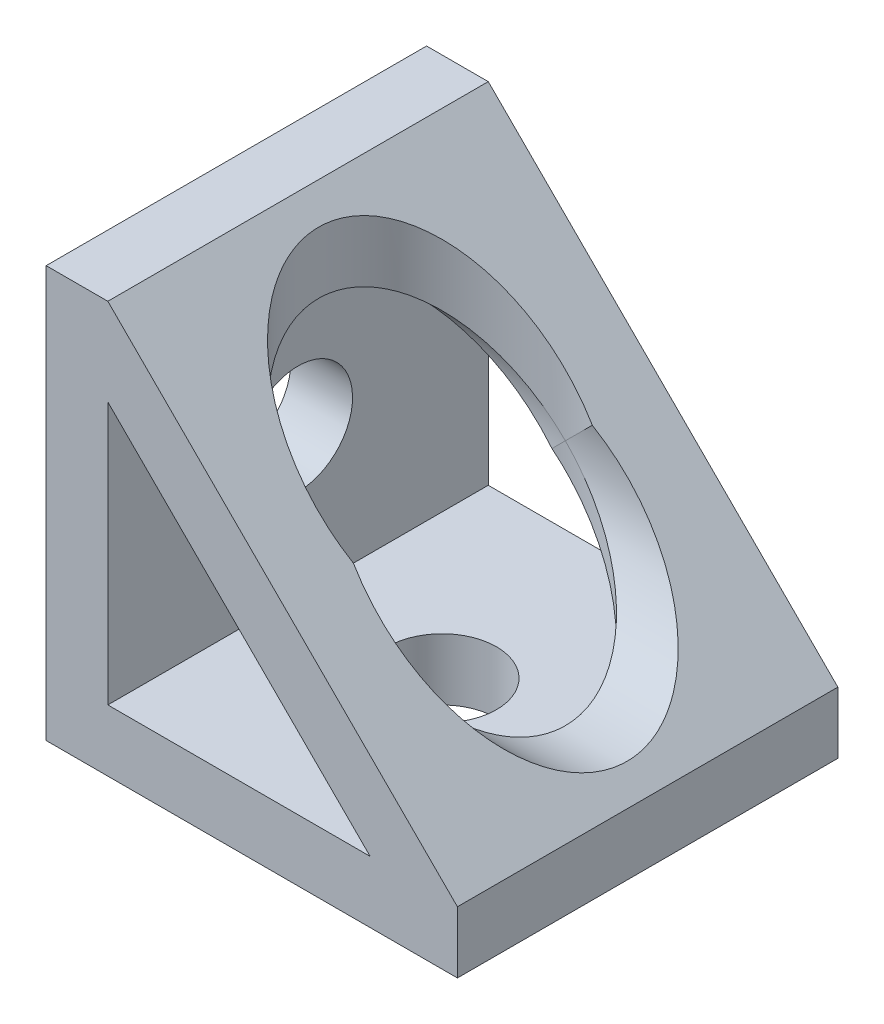
SolidWorks part; units mm, degrees
ref_plane "Front Plane" through (0, 0, 0) normal (0, 0, 1) x (1, 0, 0)
ref_plane "Top Plane" through (0, 0, 0) normal (0, 1, 0) x (1, 0, 0)
ref_plane "Right Plane" through (0, 0, 0) normal (1, 0, 0) x (0, 0, -1)
sketch "Sketch1" plane through (0, 0, 0) normal (0, 0, 1) x (1, 0, 0)
  line L0 (0, 10) -> (0, -10) construction
  line L1 (10, 0) -> (-10, 0) construction
  line L2 (-2.65, -10) -> (2.65, -10) construction
  line L3 (-10, -10) -> (-10, -7) construction
  line L4 (-6, -7) -> (6, -7) construction
  point P4 (0, 0)
  point P8 (0, 0)
  point P11 (0, -10)
  point P16 (0, -7)
  dimension "Length" = 20
  dimension "Clearance Hole" = 5.3
  dimension "Wall" = 3
  dimension "Access Hole" = 12
  dimension "For Rail Height" = 20
sketch "Sketch3" plane through (0, 0, 0) normal (1, 0, 0) x (0, 0, -1)
  line L0 (9.25, 0) -> (-9.25, 0) construction
  point P3 (0, 0)
  dimension "Thickness" = 18.5
sketch "Sketch2" plane through (0, 0, 0) normal (0, 0, 1) x (1, 0, 0)
  line L0 (-10, 10) -> (-10, -10)
  line L1 (-10, -10) -> (10, -10)
  line L3 (-2.65, -10) -> (2.65, -10) construction
  line L4 (-10, -10) -> (-10, -7) construction
  line L5 (10, -10) -> (10, -7)
  line L6 (10, -7) -> (-7, 10)
  line L7 (-7, 10) -> (-10, 10)
  line L8 (-7, 5.7574) -> (-7, -7)
  line L9 (-7, -7) -> (5.7574, -7)
  line L10 (5.7574, -7) -> (5.7574, -7)
  line L11 (5.7574, -7) -> (-7, 5.7574)
  line L12 (-7, 5.7574) -> (-7, 5.7574)
extrude "Boss-Extrude1" add sketch "Sketch2" against normal up to vertex (9.25 mm away) and the other way up to vertex (9.25 mm away) up to point (0, 0, -9.25) other way up to point (0, 0, 9.25)
sketch "Sketch4" plane through (0, -10, 0) normal (0, -1, 0) x (1, 0, 0)
  line L0 (-2.65, 0) -> (2.65, 0) construction
  line L1 (-2.65, 0) -> (2.65, 0) construction
  circle A0 centre (0, 0) radius 2.65
extrude "Cut-Extrude1" cut sketch "Sketch4" against normal up to next
sketch "Sketch6" plane through (0, -7, 0) normal (0, 1, 0) x (1, 0, 0)
  circle A0 centre (0, 0) radius 6
extrude "Cut-Extrude2" cut sketch "Sketch6" along normal through all
ref_plane "Plane1" through (0, 0, 0) normal (0.7071, -0.7071, 0) x (-0.7071, -0.7071, 0)
mirror "Mirror1" about plane through (0, 0, 0) normal (0.7071, -0.7071, 0) of "Cut-Extrude2", "Cut-Extrude1"
sketch "Sketch7" plane through (0, -7, 0) normal (0, 1, 0) x (1, 0, 0)
  line L0 (0, 0) -> (2.295, 1.325) construction
  line L1 (10, -9.25) -> (-7, -9.25) construction
  circle A0 centre (0, 0) radius 2.65 construction
  dimension "D1" = 30
sketch "Sketch8" plane through (-7, 0, 0) normal (1, 0, 0) x (0, 0, -1)
  line L0 (0, 0) -> (-1.8738, 1.8738) construction
  line L1 (9.25, -10) -> (-9.25, -10) construction
  circle A0 centre (0, 0) radius 2.65 construction
  dimension "D1" = 45
